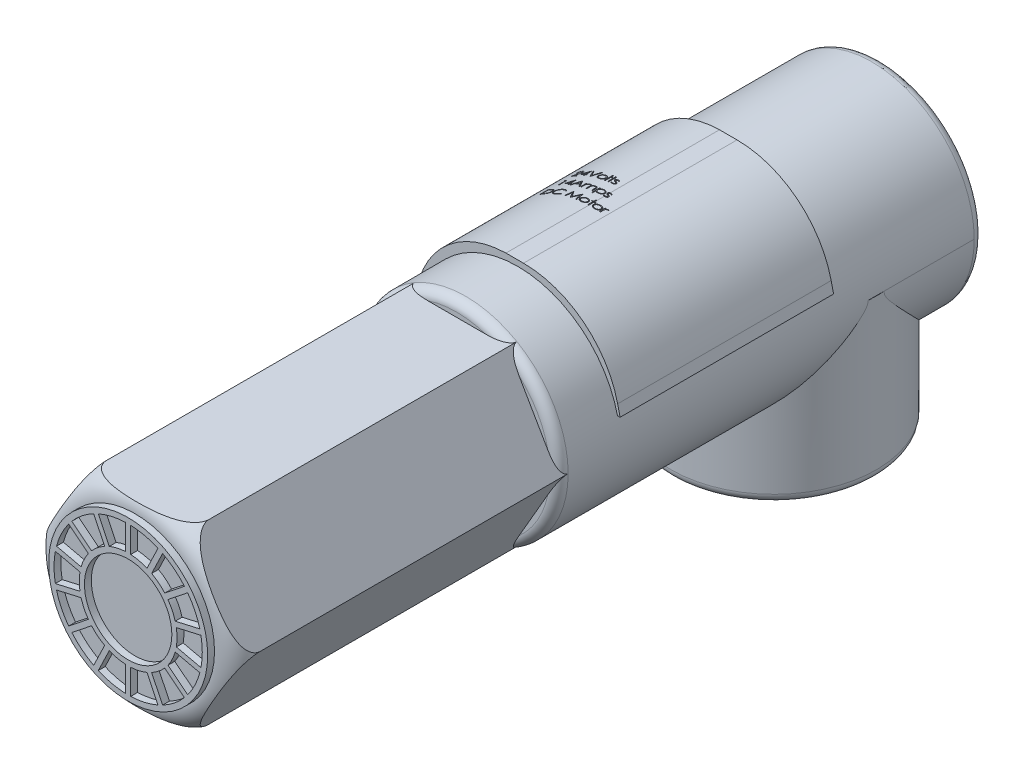
SolidWorks part; units mm, degrees
ref_plane "Front Plane" through (0, 0, 0) normal (0, 0, 1) x (1, 0, 0)
ref_plane "Top Plane" through (0, 0, 0) normal (0, 1, 0) x (1, 0, 0)
ref_plane "Right Plane" through (0, 0, 0) normal (1, 0, 0) x (0, 0, -1)
sketch "Sketch1" plane through (0, 0, 0) normal (0, 1, 0) x (1, 0, 0)
  circle A0 centre (0, 0) radius 45
  dimension "D1" = 90
extrude "Boss-Extrude1" add sketch "Sketch1" along normal blind 70
sketch "Sketch2" plane through (0, 0, 0) normal (0, -1, 0) x (1, 0, 0)
  circle A0 centre (0, 0) radius 15
  dimension "D1" = 30
extrude "Boss-Extrude2" add sketch "Sketch2" along normal blind 15
sketch "Sketch3" plane through (0, 0, 0) normal (0, 0, 1) x (1, 0, 0)
  line L0 (45, 70) -> (-45, 70) construction
  circle A0 centre (0, 70) radius 44.8663
extrude "Boss-Extrude3" add sketch "Sketch3" along normal blind 280 and the other way blind 47
fillet "Fillet1" radius 10 1 edges at (44.8663, 70, 280)
sketch "Sketch5" plane through (0, 0, 280) normal (0, 0, 1) x (1, 0, 0)
  line L3 (22.4331, 108.8553) -> (-22.4331, 108.8553)
  line L4 (-22.4331, 108.8553) -> (-44.8663, 70)
  line L5 (-44.8663, 70) -> (-22.4331, 31.1447)
  line L6 (-22.4331, 31.1447) -> (22.4331, 31.1447)
  line L7 (22.4331, 31.1447) -> (44.8663, 70)
  line L8 (44.8663, 70) -> (22.4331, 108.8553)
  circle A0 centre (0, 70) radius 44.8663 construction
  circle A2 centre (0, 70) radius 44.8663
extrude "Cut-Extrude1" cut sketch "Sketch5" against normal blind 141 contours L4 A2 | L3 A2 | L8 A2 | L7 A2 | L6 A2 | L5 A2 region at (35.7444, 90.637, 280) region at (0, 111.2741, 280) region at (-35.7444, 90.637, 280) region at (35.7444, 49.363, 280) region at (-35.7444, 49.363, 280) region at (0, 28.7259, 280)
fillet "Fillet2" radius 4 6 edges at (0, 114.8663, 139) (38.8553, 92.4331, 139) (38.8553, 47.5669, 139) (0, 25.1337, 139) (-38.8553, 47.5669, 139) (-38.8553, 92.4331, 139)
fillet "Fillet3" radius 4 1 edges at (44.8663, 70, -47)
fillet "Fillet4" radius 4 2 edges at (0, 0, 45) (0, 0, -15)
sketch "Sketch6" plane through (0, 0, 280) normal (0, 0, 1) x (1, 0, 0)
  line L0 (10.3007, 88.8091) -> (15.0987, 98.7722)
  line L1 (8.2832, 89.7807) -> (13.0811, 99.7438)
  line L3 (-1.1197, 91.4158) -> (-1.1197, 102.474)
  line L5 (1.1197, 91.4158) -> (1.1197, 102.474)
  line L6 (17.4416, 82.4771) -> (26.0873, 89.3718)
  line L7 (16.0454, 84.2279) -> (24.6911, 91.1226)
  line L8 (21.128, 73.6739) -> (31.9089, 76.1345)
  line L9 (20.6297, 75.857) -> (31.4106, 78.3177)
  line L10 (20.6297, 64.143) -> (31.4106, 61.6823)
  line L11 (21.128, 66.3261) -> (31.9089, 63.8655)
  line L12 (16.0454, 55.7721) -> (24.6911, 48.8774)
  line L13 (17.4416, 57.5229) -> (26.0873, 50.6282)
  line L14 (8.2832, 50.2193) -> (13.0811, 40.2562)
  line L15 (10.3007, 51.1909) -> (15.0987, 41.2278)
  line L16 (-1.1197, 48.5842) -> (-1.1197, 37.526)
  line L17 (1.1197, 48.5842) -> (1.1197, 37.526)
  line L18 (-10.3007, 51.1909) -> (-15.0987, 41.2278)
  line L19 (-8.2832, 50.2193) -> (-13.0811, 40.2562)
  line L20 (-17.4416, 57.5229) -> (-26.0873, 50.6282)
  line L21 (-16.0454, 55.7721) -> (-24.6911, 48.8774)
  line L22 (-21.128, 66.3261) -> (-31.9089, 63.8655)
  line L23 (-20.6297, 64.143) -> (-31.4106, 61.6823)
  line L24 (-20.6297, 75.857) -> (-31.4106, 78.3177)
  line L25 (-21.128, 73.6739) -> (-31.9089, 76.1345)
  line L26 (-16.0454, 84.2279) -> (-24.6911, 91.1226)
  line L27 (-17.4416, 82.4771) -> (-26.0873, 89.3718)
  line L28 (-8.2832, 89.7807) -> (-13.0811, 99.7438)
  line L29 (-10.3007, 88.8091) -> (-15.0987, 98.7722)
  circle A1 centre (0, 70) radius 34.8663
  arc A2 (1.1197, 104.8483) -> (-1.1197, 104.8483) centre (0, 70) ccw
  arc A3 (16.1289, 100.9114) -> (14.1113, 101.883) centre (0, 70) ccw
  arc A5 (27.9436, 90.8522) -> (26.5474, 92.6029) centre (0, 70) ccw
  arc A7 (34.2237, 76.6629) -> (33.7254, 78.8461) centre (0, 70) ccw
  arc A9 (33.7254, 61.1539) -> (34.2237, 63.3371) centre (0, 70) ccw
  arc A11 (26.5474, 47.3971) -> (27.9436, 49.1478) centre (0, 70) ccw
  arc A13 (14.1113, 38.117) -> (16.1289, 39.0886) centre (0, 70) ccw
  arc A15 (-1.1197, 35.1517) -> (1.1197, 35.1517) centre (0, 70) ccw
  arc A17 (-16.1289, 39.0886) -> (-14.1113, 38.117) centre (0, 70) ccw
  arc A19 (-27.9436, 49.1478) -> (-26.5474, 47.3971) centre (0, 70) ccw
  arc A21 (-34.2237, 63.3371) -> (-33.7254, 61.1539) centre (0, 70) ccw
  arc A23 (-33.7254, 78.8461) -> (-34.2237, 76.6629) centre (0, 70) ccw
  arc A25 (-26.5474, 92.6029) -> (-27.9436, 90.8522) centre (0, 70) ccw
  arc A27 (-14.1113, 101.883) -> (-16.1289, 100.9114) centre (0, 70) ccw
  arc A29 (21.128, 66.3261) -> (21.128, 73.6739) centre (0, 70) ccw
  arc A30 (-21.128, 73.6739) -> (-21.128, 66.3261) centre (0, 70) ccw
  circle A31 centre (0, 70) radius 19.1604
  arc A32 (-31.9089, 76.1345) -> (-31.9089, 63.8655) centre (0, 70) ccw
  circle A33 centre (0, 70) radius 34.8663
  arc A40 (17.4416, 57.5229) -> (20.6297, 64.143) centre (0, 70) ccw
  arc A41 (10.3007, 51.1909) -> (16.0454, 55.7721) centre (0, 70) ccw
  arc A42 (1.1197, 48.5842) -> (8.2832, 50.2193) centre (0, 70) ccw
  arc A43 (-8.2832, 50.2193) -> (-1.1197, 48.5842) centre (0, 70) ccw
  arc A44 (-16.0454, 55.7721) -> (-10.3007, 51.1909) centre (0, 70) ccw
  arc A46 (-20.6297, 64.143) -> (-17.4416, 57.5229) centre (0, 70) ccw
  arc A48 (-17.4416, 82.4771) -> (-20.6297, 75.857) centre (0, 70) ccw
  arc A50 (-10.3007, 88.8091) -> (-16.0454, 84.2279) centre (0, 70) ccw
  arc A52 (-1.1197, 91.4158) -> (-8.2832, 89.7807) centre (0, 70) ccw
  arc A53 (8.2832, 89.7807) -> (1.1197, 91.4158) centre (0, 70) ccw
  arc A54 (16.0454, 84.2279) -> (10.3007, 88.8091) centre (0, 70) ccw
  arc A55 (20.6297, 75.857) -> (17.4416, 82.4771) centre (0, 70) ccw
  arc A56 (-26.0873, 89.3718) -> (-31.4106, 78.3177) centre (0, 70) ccw
  arc A57 (24.6911, 91.1226) -> (15.0987, 98.7722) centre (0, 70) ccw
  arc A58 (13.0811, 99.7438) -> (1.1197, 102.474) centre (0, 70) ccw
  arc A59 (-1.1197, 102.474) -> (-13.0811, 99.7438) centre (0, 70) ccw
  arc A60 (-15.0987, 98.7722) -> (-24.6911, 91.1226) centre (0, 70) ccw
  arc A61 (-24.6911, 48.8774) -> (-15.0987, 41.2278) centre (0, 70) ccw
  arc A62 (-31.4106, 61.6823) -> (-26.0873, 50.6282) centre (0, 70) ccw
  arc A63 (-13.0811, 40.2562) -> (-1.1197, 37.526) centre (0, 70) ccw
  arc A64 (1.1197, 37.526) -> (13.0811, 40.2562) centre (0, 70) ccw
  arc A65 (15.0987, 41.2278) -> (24.6911, 48.8774) centre (0, 70) ccw
  arc A66 (26.0873, 50.6282) -> (31.4106, 61.6823) centre (0, 70) ccw
  arc A67 (31.9089, 63.8655) -> (31.9089, 76.1345) centre (0, 70) ccw
  arc A68 (31.4106, 78.3177) -> (26.0873, 89.3718) centre (0, 70) ccw
  point P1 (0, 90.0543)
  point P63 (0, 70)
  circle M3 centre (0, 70) radius 34.8663
  dimension "D1" = 0
  dimension "D2" = 14
extrude "Boss-Extrude4" add sketch "Sketch6" along normal blind 3 contours A68 L9 A55 L6 A67 L11 A29 L8 A66 L13 A40 L10 A65 L15 A41 L12 A64 L17 M3 region at (33.7236, 66.7478, 280)
ref_plane "Plane1" through (0, 80, 0) normal (0, 1, 0) x (1, 0, 0)
sketch "Sketch7" plane through (0, 80, 0) normal (0, 1, 0) x (1, 0, 0)
  line L0 (-44.8663, -18.6493) -> (44.8663, -18.6493)
  line L1 (-44.8663, -3.4668) -> (-44.8663, -135) construction
  line L2 (44.8663, -135) -> (44.8663, -3.4668) construction
  line L3 (44.8663, -18.6493) -> (44.8663, -112.2442)
  line L4 (44.8663, -112.2442) -> (-44.8663, -112.2442)
  line L5 (-44.8663, -112.2442) -> (-44.8663, -18.6493)
extrude "Boss-Extrude5" add sketch "Sketch7" along normal blind 72
sketch "Sketch8" plane through (0, 0, 0) normal (0, 0, 1) x (1, 0, 0)
  line L0 (44.8663, 80) -> (43.8041, 84.564)
  line L1 (56.7972, 80) -> (-56.7972, 80) construction
  line L2 (44.8663, 152) -> (44.8663, 80) construction
  line L3 (-44.9297, 80) -> (-44.0554, 84.564)
  line L4 (-5.1525, 117.3232) -> (2.5453, 117.3232)
  line L5 (44.8663, 80) -> (50.6886, 80)
  line L6 (50.6886, 80) -> (50.6886, 163.3534)
  line L7 (50.6886, 163.3534) -> (-52.5791, 163.3534)
  line L8 (-52.5791, 163.3534) -> (-51.3771, 80)
  line L9 (-51.3771, 80) -> (-44.9297, 80)
  arc A0 (43.8041, 84.564) -> (2.5453, 117.3232) centre (2.5453, 74.9617) ccw
  arc A1 (-44.0554, 84.564) -> (-5.1525, 117.3232) centre (-4.4178, 76.9716) cw
extrude "Cut-Extrude2" cut sketch "Sketch8" along normal blind 166
ref_plane "Plane2" through (0, 150, 0) normal (0, 1, 0) x (1, 0, 0)
sketch "Sketch9" plane through (0, 150, 0) normal (0, 1, 0) x (1, 0, 0)
  text T0 "24Volts\r\n14Amps\r\nDC Motor" font "Century Gothic" height 3.5
extrude "Cut-Extrude3" cut sketch "Sketch9" against normal blind 61
